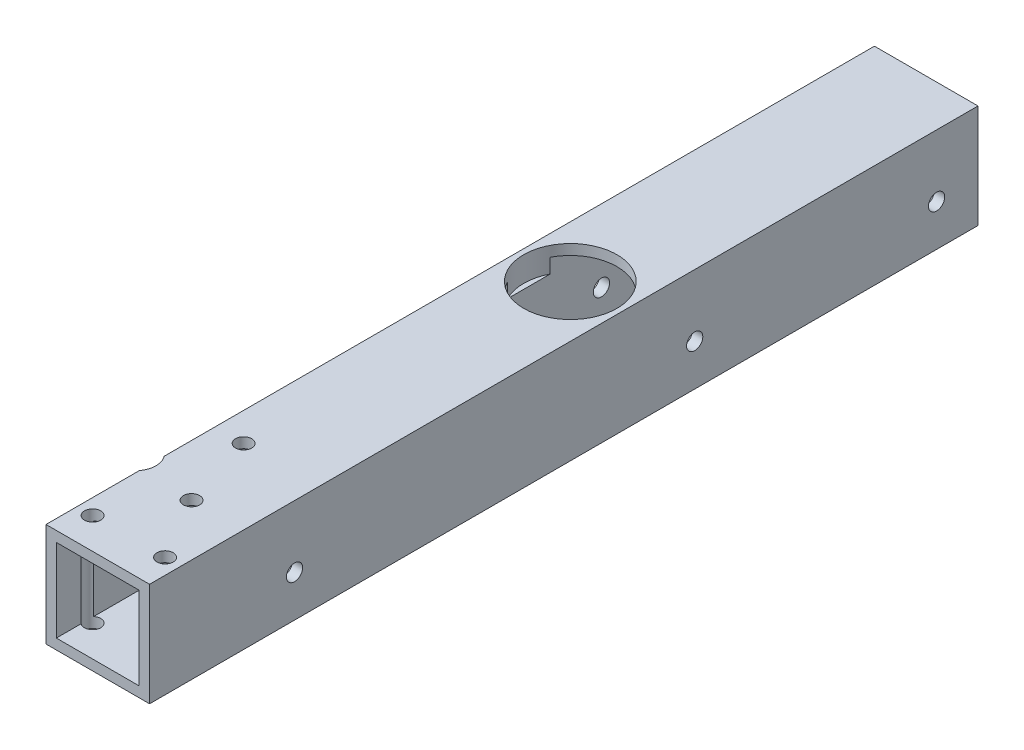
SolidWorks part; units mm, degrees
material "6061 Alloy"
ref_plane "Front Plane" through (0, 0, 0) normal (0, 0, 1) x (1, 0, 0)
ref_plane "Top Plane" through (0, 0, 0) normal (0, 1, 0) x (1, 0, 0)
ref_plane "Right Plane" through (0, 0, 0) normal (1, 0, 0) x (0, 0, -1)
sketch "Sketch1" plane through (0, 0, 0) normal (0, 0, 1) x (1, 0, 0)
  line L0 (-12.7, 12.7) -> (12.7, 12.7)
  line L2 (-15.875, 15.875) -> (15.875, 15.875)
  line L3 (-15.875, 15.875) -> (-15.875, -15.875)
  line L4 (-15.875, -15.875) -> (15.875, -15.875)
  line L5 (15.875, 15.875) -> (15.875, -15.875)
  line L10 (12.7, 12.7) -> (12.7, -12.7)
  line L11 (-12.7, -12.7) -> (12.7, -12.7)
  line L12 (-12.7, 12.7) -> (-12.7, -12.7)
  point P12 (0, 15.875)
  point P14 (15.875, 0)
  dimension "Wall Thickness" = 3.175
  dimension "Outside Width" = 31.75
  dimension "Outside Height" = 31.75
  dimension "Inside Height" = 25.4
  dimension "Inside Width" = 25.4
sketch "Sketch2" plane through (0, 0, 0) normal (1, 0, 0) x (0, 0, -1)
  line L0 (127, 0) -> (-127, 0)
  point P4 (0, 0)
  point P7 (-127, 0)
  point P10 (127, 0)
  dimension "Length" = 254
sketch "Sketch3" plane through (0, 0, 0) normal (0, 0, 1) x (1, 0, 0)
  line L21 (15.875, 15.875) -> (-15.875, 15.875)
  line L22 (15.875, -15.875) -> (15.875, 15.875)
  line L23 (-15.875, -15.875) -> (15.875, -15.875)
  line L24 (-15.875, 15.875) -> (-15.875, -15.875)
  line L25 (15.875, 15.875) -> (-15.875, 15.875)
  line L26 (15.875, -15.875) -> (15.875, 15.875)
  line L27 (-15.875, -15.875) -> (15.875, -15.875)
  line L28 (-15.875, 15.875) -> (-15.875, -15.875)
  line L29 (12.7, 12.7) -> (-12.7, 12.7)
  line L30 (12.7, -12.7) -> (12.7, 12.7)
  line L31 (-12.7, -12.7) -> (12.7, -12.7)
  line L32 (-12.7, 12.7) -> (-12.7, -12.7)
  line L33 (12.7, 12.7) -> (-12.7, 12.7)
  line L34 (12.7, -12.7) -> (12.7, 12.7)
  line L35 (-12.7, -12.7) -> (12.7, -12.7)
  line L36 (-12.7, 12.7) -> (-12.7, -12.7)
  dimension "D1" = 0
  dimension "D2" = 0
extrude "Boss-Extrude1" add sketch "Sketch3" along normal up to vertex (127 mm away) and the other way up to vertex (127 mm away) up to point (0, 0, 127) other way up to point (0, 0, -127)
sketch "Drawing Reference" plane through (0, 0, 0) normal (1, 0, 0) x (0, 0, -1)
  line L0 (-127, 0) -> (127, 0) construction
  line L1 (0, -15.875) -> (0, 15.875) construction
  line L2 (-127, -15.875) -> (127, -15.875) construction
  line L5 (-127, 15.875) -> (127, 15.875) construction
  point P7 (-104.14, 0)
  point P8 (104.14, 0)
  dimension "D1" = 22.86
sketch "Sketch4" plane through (0, 15.875, 0) normal (0, 1, 0) x (1, 0, 0)
  line L0 (0, -127) -> (0, -117.475) construction
  line L1 (15.875, -127) -> (-15.875, -127) construction
  line L2 (0, -117.475) -> (11.1125, -117.475) construction
  line L3 (0, -117.475) -> (-11.1125, -117.475) construction
  line L4 (0, -117.475) -> (0, 17.8816) construction
  line L5 (0, -117.475) -> (0, -98.2472) construction
  point P5 (-7.1119, -75.1713)
  dimension "D1" = 135.3566
  dimension "D2" = 22.225
  dimension "D3" = 9.525
hole_wizard "#10 Clearance Hole1" positions "Sketch5" profile "Sketch6" hole size "#10" standard "ANSI Inch" end condition through all
sketch "Sketch5" plane through (0, 15.875, 0) normal (0, 1, 0) x (1, 0, 0)
  point P0 (-11.1125, -117.475)
  point P3 (11.1125, -117.475)
  point P7 (0, -98.2472)
  point P10 (-7.1119, -75.1713)
sketch "Sketch6" plane through (-11.1125, 15.875, 117.475) normal (1, 0, 0) x (0, 0, 1)
  line L0 (0, 0) -> (0, 31.75)
  line L1 (0, 31.75) -> (2.4892, 31.75)
  line L2 (2.4892, 31.75) -> (2.4892, 0)
  line L5 (2.4892, 0) -> (0, 0)
  line L11 (0, -6.35) -> (0, 107.95) construction
  dimension "Thru Hole Dia." = 4.9784
  dimension "Thru Hole Depth" = 31.75
sketch "Sketch7" plane through (0, 15.875, 0) normal (0, 1, 0) x (1, 0, 0)
  circle A0 centre (0, 17.8816) radius 14.2875
  dimension "D1" = 28.575
extrude "Cut-Extrude1" cut sketch "Sketch7" against normal blind 7.62
sketch "Sketch8" plane through (0, -15.875, 0) normal (0, -1, 0) x (1, 0, 0)
  circle A0 centre (0, -17.8816) radius 14.2875
  dimension "D1" = 28.575
extrude "Cut-Extrude2" cut sketch "Sketch8" against normal blind 7.62
sketch "Sketch9" plane through (15.875, 0, 0) normal (1, 0, 0) x (0, 0, -1)
  line L0 (-127, -3.175) -> (-82.55, -3.175) construction
  line L2 (-82.55, -3.175) -> (114.3, -3.175) construction
  line L3 (-127, 15.875) -> (-127, -3.175) construction
  line L4 (52.832, -3.175) -> (40.132, -3.175) construction
  line L5 (52.832, 10.4775) -> (52.832, -434.0225) construction
  dimension "D1" = 44.45
  dimension "D2" = 19.05
  dimension "D3" = 12.7
hole_wizard "#10 Clearance Hole2" positions "Sketch10" profile "Sketch11" hole size "#10" standard "ANSI Inch" end condition through all
sketch "Sketch10" plane through (15.875, 0, 0) normal (1, 0, 0) x (0, 0, -1)
  point P0 (-82.55, -3.175)
  point P4 (114.3, -3.175)
  point P8 (40.132, -3.175)
sketch "Sketch11" plane through (15.875, -3.175, 82.55) normal (0, 1, 0) x (0, 0, -1)
  line L0 (0, 0) -> (0, 31.75)
  line L1 (0, 31.75) -> (2.4892, 31.75)
  line L2 (2.4892, 31.75) -> (2.4892, 0)
  line L5 (2.4892, 0) -> (0, 0)
  line L11 (0, -6.35) -> (0, 107.95) construction
  dimension "Thru Hole Dia." = 4.9784
  dimension "Thru Hole Depth" = 31.75
sketch "Sketch12" plane through (0, 15.875, 0) normal (0, 1, 0) x (1, 0, 0)
  line L0 (-20.955, -94.5576) -> (-15.875, -94.5576) construction
  line L1 (-15.875, -127) -> (-15.875, 127) construction
  circle A0 centre (-20.955, -94.5576) radius 6.35
  dimension "D1" = 5.08
extrude "Cut-Extrude3" cut sketch "Sketch12" against normal through all
equation "\"D1@Drawing Reference\"=\"Outside Width@Sketch1\" * 0.72"
